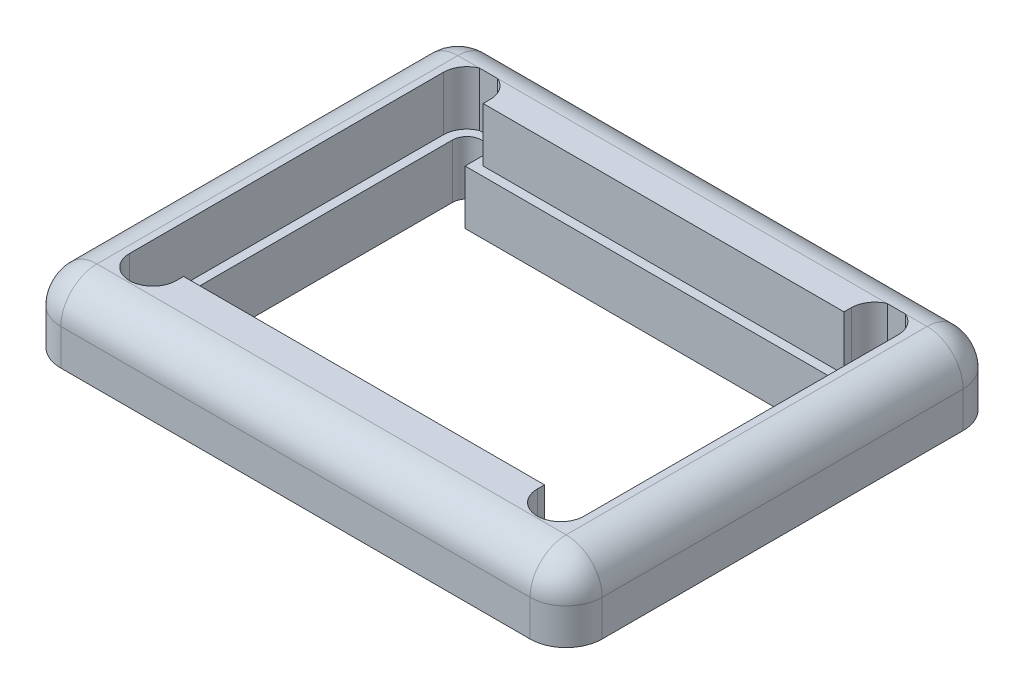
SolidWorks part; units mm, degrees
ref_plane "Front Plane" through (0, 0, 0) normal (0, 0, 1) x (1, 0, 0)
ref_plane "Top Plane" through (0, 0, 0) normal (0, 1, 0) x (1, 0, 0)
ref_plane "Right Plane" through (0, 0, 0) normal (1, 0, 0) x (0, 0, -1)
sketch "Sketch2" plane through (0, 0, 0) normal (0, 1, 0) x (1, 0, 0)
  line L1 (-75, -60) -> (75, -60)
  line L2 (-75, -60) -> (-75, 60)
  line L3 (-75, 60) -> (75, 60)
  line L4 (75, -60) -> (75, 60)
  line L5 (-75, -60) -> (75, 60) construction
  line L6 (-75, 60) -> (75, -60) construction
  point P0 (0, 0)
  dimension "D1" = 150
  dimension "D2" = 120
extrude "Boss-Extrude1" add sketch "Sketch2" along normal blind 20
fillet "Fillet1" radius 10 8 edges at (0, 20, 60) (-75, 20, 0) (0, 20, -60) (75, 20, 0) (75, 10, -60) (-75, 10, -60) (-75, 10, 60) (75, 10, 60)
sketch "Sketch3" plane through (0, 0, 0) normal (0, -1, 0) x (1, 0, 0)
  line L0 (-64.75, 39.75) -> (-64.75, -39.75)
  line L1 (-54.75, -49.75) -> (54.75, -49.75)
  line L2 (64.75, -39.75) -> (64.75, 39.75)
  line L3 (54.75, 49.75) -> (-54.75, 49.75)
  line L4 (-65, -60) -> (65, -60)
  line L5 (75, -50) -> (75, 50)
  line L6 (65, 60) -> (-65, 60)
  line L7 (-75, 50) -> (-75, -50)
  line L8 (-65, -60) -> (65, -60)
  line L9 (75, -50) -> (75, 50)
  line L10 (65, 60) -> (-65, 60)
  line L11 (-75, 50) -> (-75, -50)
  line L12 (-64.75, 49.75) -> (-64.75, -49.75) construction
  line L13 (-64.75, -49.75) -> (64.75, -49.75) construction
  line L14 (64.75, -49.75) -> (64.75, 49.75) construction
  line L15 (64.75, 49.75) -> (-64.75, 49.75) construction
  arc A4 (65, -60) -> (75, -50) centre (65, -50) ccw
  arc A5 (75, 50) -> (65, 60) centre (65, 50) ccw
  arc A6 (-65, 60) -> (-75, 50) centre (-65, 50) ccw
  arc A7 (-75, -50) -> (-65, -60) centre (-65, -50) ccw
  arc A8 (65, -60) -> (75, -50) centre (65, -50) ccw
  arc A9 (75, 50) -> (65, 60) centre (65, 50) ccw
  arc A10 (-65, 60) -> (-75, 50) centre (-65, 50) ccw
  arc A11 (-75, -50) -> (-65, -60) centre (-65, -50) ccw
  arc A12 (-64.75, -39.75) -> (-54.75, -49.75) centre (-54.75, -39.75) ccw
  arc A13 (-64.75, -49.75) -> (-64.75, -49.75) centre (-64.75, -49.75) ccw construction
  arc A14 (64.75, -39.75) -> (54.75, -49.75) centre (54.75, -39.75) cw
  arc A15 (64.75, -49.75) -> (64.75, -49.75) centre (64.75, -49.75) ccw construction
  arc A16 (64.75, 39.75) -> (54.75, 49.75) centre (54.75, 39.75) ccw
  arc A17 (64.75, 49.75) -> (64.75, 49.75) centre (64.75, 49.75) ccw construction
  arc A18 (-64.75, 39.75) -> (-54.75, 49.75) centre (-54.75, 39.75) cw
  arc A19 (-64.75, 49.75) -> (-64.75, 49.75) centre (-64.75, 49.75) ccw construction
  dimension "D3" = 10
  dimension "D1" = 0
  dimension "D2" = 10.25
extrude "Boss-Extrude2" add sketch "Sketch3" along normal blind 10 contours A18 L0 A12 L1 A14 L2 A16 L3 region at (0, 0, 0)
sketch "Sketch4" plane through (0, 20, 0) normal (0, 1, 0) x (1, 0, 0)
  line L0 (-50, -41) -> (50, -41)
  line L1 (50, -41) -> (50, -43)
  line L2 (63, -43) -> (63, 44)
  line L3 (50, 44) -> (50, 42)
  line L4 (50, 42) -> (-50, 42)
  line L5 (-50, 42) -> (-50, 44)
  line L6 (-63, 44) -> (-63, -43)
  line L7 (-50, -43) -> (-50, -41)
  line L8 (52.5, 44) -> (52.5, 39.5)
  line L9 (52.5, 39.5) -> (-52.5, 39.5)
  line L10 (-52.5, 39.5) -> (-52.5, 44)
  line L11 (-60.5, 44) -> (-60.5, -43)
  line L12 (-52.5, -43) -> (-52.5, -38.5)
  line L13 (-52.5, -38.5) -> (52.5, -38.5)
  line L14 (52.5, -38.5) -> (52.5, -43)
  line L15 (60.5, -43) -> (60.5, 44)
  line L16 (52.5, 44) -> (52.5, 39.5)
  line L17 (52.5, 39.5) -> (-52.5, 39.5)
  line L18 (-52.5, 39.5) -> (-52.5, 44)
  line L19 (-60.5, 44) -> (-60.5, -43)
  line L20 (-52.5, -43) -> (-52.5, -38.5)
  line L21 (-52.5, -38.5) -> (52.5, -38.5)
  line L22 (52.5, -38.5) -> (52.5, -43)
  line L23 (60.5, -43) -> (60.5, 44)
  line L24 (49.5, 42.5) -> (-49.5, 42.5)
  line L25 (-49.5, 42.5) -> (-49.5, 44)
  line L26 (-63.5, 44) -> (-63.5, -43)
  line L27 (-49.5, -43) -> (-49.5, -41.5)
  line L28 (-49.5, -41.5) -> (49.5, -41.5)
  line L29 (49.5, -41.5) -> (49.5, -43)
  line L30 (63.5, -43) -> (63.5, 44)
  line L31 (49.5, 44) -> (49.5, 42.5)
  arc A0 (50, -43) -> (63, -43) centre (56.5, -43) ccw
  arc A1 (63, 44) -> (50, 44) centre (56.5, 44) ccw
  arc A2 (-50, 44) -> (-63, 44) centre (-56.5, 44) ccw
  arc A3 (-63, -43) -> (-50, -43) centre (-56.5, -43) ccw
  arc A4 (60.5, 44) -> (52.5, 44) centre (56.5, 44) ccw
  arc A5 (-52.5, 44) -> (-60.5, 44) centre (-56.5, 44) ccw
  arc A6 (-60.5, -43) -> (-52.5, -43) centre (-56.5, -43) ccw
  arc A7 (52.5, -43) -> (60.5, -43) centre (56.5, -43) ccw
  arc A8 (60.5, 44) -> (52.5, 44) centre (56.5, 44) ccw
  arc A9 (-52.5, 44) -> (-60.5, 44) centre (-56.5, 44) ccw
  arc A10 (-60.5, -43) -> (-52.5, -43) centre (-56.5, -43) ccw
  arc A11 (52.5, -43) -> (60.5, -43) centre (56.5, -43) ccw
  arc A12 (-49.5, 44) -> (-63.5, 44) centre (-56.5, 44) ccw
  arc A13 (-63.5, -43) -> (-49.5, -43) centre (-56.5, -43) ccw
  arc A14 (49.5, -43) -> (63.5, -43) centre (56.5, -43) ccw
  arc A15 (63.5, 44) -> (49.5, 44) centre (56.5, 44) ccw
  line M28 (65, 50) -> (-65, 50)
  dimension "D1" = 0
  dimension "D2" = 2.5
  dimension "D3" = 3
extrude "Cut-Extrude1" cut sketch "Sketch4" against normal up to surface (30 mm away) contours L22 A11 L23 A8 L16 L17 L18 A9 L19 A10 L20 L21 region at (0, 20, -0.5) up to face at (0, -10, 0)
extrude "Cut-Extrude2" cut sketch "Sketch4<3>" against normal blind 15 contours L6 A3 L7 L0 L1 A0 L2 A1 L3 L4 L5 A2 A11 L22 L21 L20 A10 L19 A9 L18 L17 L16 A8 L23 M28 region at (-51.6055, 20, 42)
sketch "Sketch4<3>" plane through (0, 20, 0) normal (0, 1, 0) x (1, 0, 0) same geometry as "Sketch4"
